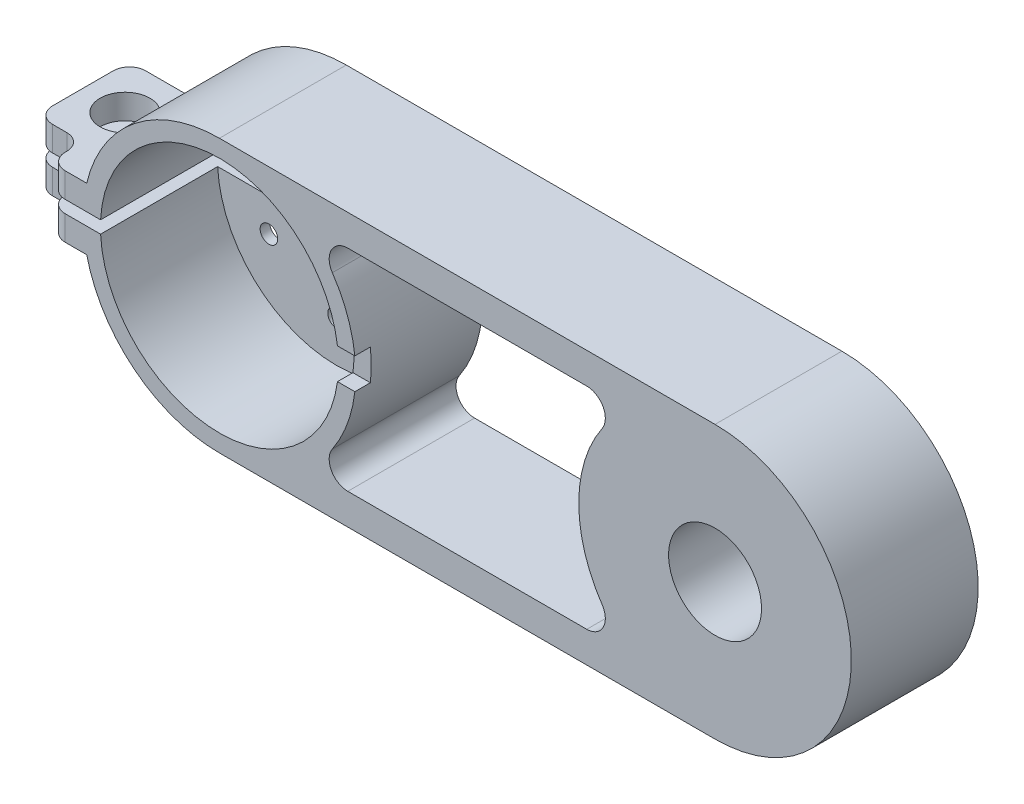
SolidWorks part; units mm, degrees
ref_plane "Front Plane" through (0, 0, 0) normal (0, 0, 1) x (1, 0, 0)
ref_plane "Top Plane" through (0, 0, 0) normal (0, 1, 0) x (1, 0, 0)
ref_plane "Right Plane" through (0, 0, 0) normal (1, 0, 0) x (0, 0, -1)
sketch "Sketch1" plane through (0, 0, 0) normal (0, 0, 1) x (1, 0, 0)
  line L0 (25.4, 0) -> (-25.4, 0) construction
  line L5 (25.4, -13.97) -> (-25.4, -13.97)
  line L6 (25.4, 13.97) -> (-25.4, 13.97)
  circle A0 centre (-25.4, 0) radius 8 construction
  arc A1 (25.4, -13.97) -> (25.4, 13.97) centre (25.4, 0) ccw
  arc A2 (-25.4, 13.97) -> (-25.4, -13.97) centre (-25.4, 0) ccw
  circle A3 centre (-25.4, 0) radius 12.7 construction
  circle A4 centre (25.4, 0) radius 38.1 construction
  circle A5 centre (-25.4, 0) radius 12.2
  point P2 (0, 0)
  dimension "D1" = 24.4
  dimension "mount spacing" = 16
  dimension "motor gear" = 25.4
  dimension "input gear" = 76.2
  dimension "D2" = 27.94
extrude "Boss-Extrude1" add sketch "Sketch1" along normal blind 13 contours A5 | L6 A2 L5 A1 A5 region at (7.5897, 0, 0) region at (-25.4, 0, 0)
hole_wizard "M1.6 Clearance Hole2" positions "Sketch4" profile "Sketch3" hole size "M1.6" standard "_Gentex Metric" end condition through all
sketch "Sketch4" plane through (0, 0, 13) normal (0, 0, 1) x (1, 0, 0)
  circle A0 centre (-25.4, 0) radius 8 construction
  point P5 (-25.4, 8)
  point P15 (-18.4718, 4)
  point P16 (-18.4718, -4)
  point P17 (-25.4, -8)
  point P18 (-32.3282, -4)
  point P19 (-32.3282, 4)
  dimension "D1" = 16
  dimension "D2" = 6
sketch "Sketch3" plane through (-32.3282, 4, 13) normal (1, 0, 0) x (0, -1, 0)
  line L0 (0, 0) -> (0, 13)
  line L1 (0, 13) -> (0.9, 13)
  line L2 (0.9, 13) -> (0.9, 0)
  line L5 (0.9, 0) -> (0, 0)
  line L11 (0, -6.35) -> (0, 107.95) construction
  dimension "Thru Hole Dia." = 1.8
  dimension "Thru Hole Depth" = 13
hole_wizard "3/8 (0.375) Diameter Hole1" positions "Sketch5" profile "Sketch6" hole size "3/8" standard "_Gentex Inch" end condition through all
sketch "Sketch5" plane through (0, 0, 13) normal (0, 0, 1) x (1, 0, 0)
  point P0 (25.4, 0)
sketch "Sketch6" plane through (25.4, 0, 13) normal (1, 0, 0) x (0, -1, 0)
  line L0 (0, 0) -> (0, 13)
  line L1 (0, 13) -> (4.7625, 13)
  line L2 (4.7625, 13) -> (4.7625, 0)
  line L5 (4.7625, 0) -> (0, 0)
  line L11 (0, -6.35) -> (0, 107.95) construction
  dimension "Thru Hole Dia." = 9.525
  dimension "Thru Hole Depth" = 13
extrude "Cut-Extrude1" cut sketch "Sketch1<4>" along normal through all from offset 1 contours A5 region at (-25.4, 0, 0)
sketch "Sketch1<4>" plane through (0, 0, 0) normal (0, 0, 1) x (1, 0, 0) same geometry as "Sketch1"
sketch "Sketch7" plane through (0, 0, 0) normal (0, 1, 0) x (1, 0, 0)
  line L0 (-38.1, 0) -> (-47.625, 0)
  line L1 (-25.4, 0) -> (-39.37, 0) construction
  line L2 (-47.625, 0) -> (-47.625, -9.525)
  line L3 (-47.625, -9.525) -> (-42.8625, -9.525)
  line L4 (-42.8625, -9.525) -> (-42.8625, -13)
  line L5 (-42.8625, -13) -> (-38.1, -13)
  line L7 (-38.1, 0) -> (0, 0) construction
  line L8 (-38.1, -13) -> (-38.1, 0)
  line L9 (-39.37, -13) -> (-25.4, -13) construction
  dimension "D1" = 9.525
  dimension "D2" = 38.1
extrude "Boss-Extrude2" add sketch "Sketch7" along normal mid plane 6.35
hole_wizard "#10 Clearance Hole1" positions "Sketch12" profile "Sketch11" hole size "#10" standard "_Gentex Inch" end condition through all
sketch "Sketch12" plane through (0, -3.175, 0) normal (0, -1, 0) x (-1, 0, 0)
  line L0 (47.625, -9.525) -> (43.3147, -4.7625) construction
  line L1 (43.3147, -4.7625) -> (39.0044, 0) construction
  point P0 (43.3147, -4.7625)
sketch "Sketch11" plane through (-43.3147, -3.175, 4.7625) normal (1, 0, 0) x (0, 0, -1)
  line L0 (0, 0) -> (0, 17.145)
  line L1 (0, 17.145) -> (2.5527, 17.145)
  line L2 (2.5527, 17.145) -> (2.5527, 0)
  line L5 (2.5527, 0) -> (0, 0)
  line L11 (0, -6.35) -> (0, 107.95) construction
  dimension "Thru Hole Dia." = 5.1054
  dimension "Thru Hole Depth" = 17.145
fillet "Fillet1" radius 1.651 4 edges at (-47.625, 0, 0) (-42.8625, 0, 13) (-42.8625, 0, 9.525) (-47.625, 0, 9.525)
sketch "Sketch9" plane through (0, 0, 13) normal (0, 0, 1) x (1, 0, 0)
  line L0 (-47.625, -3.175) -> (-47.625, 3.175) construction
  line L1 (-47.625, 0.635) -> (-29.0958, 0.635)
  line L2 (-47.625, 0.635) -> (-47.625, -0.635)
  line L3 (-47.625, -0.635) -> (-29.0958, -0.635)
  line L5 (-47.625, 0.635) -> (-29.0958, -0.635) construction
  line L6 (-47.625, -0.635) -> (-29.0958, 0.635) construction
  arc A0 (-29.0958, -0.635) -> (-29.0958, 0.635) centre (-25.4, 0) ccw
  circle A1 centre (-25.4, 0) radius 12.2 construction
  arc A2 (-29.0958, 0.635) -> (-29.0958, -0.635) centre (-25.4, 0) ccw
  point P6 (-38.3604, 0)
  line M4 (-41.2115, 3.175) -> (-41.2115, -3.175)
  circle M11 centre (-25.4, 0) radius 12.2
  dimension "D1" = 7.5
  dimension "D2" = 1.27
extrude "Cut-Extrude2" cut sketch "Sketch9" against normal through all contours A0 | A0 L1 L3 M11 | L2 L3 L1 M4 | L3 L1 M4 M11 region at (-44.4183, 0, 13) region at (-39.403, 0, 13) region at (-33.3632, 0, 13) region at (-25.4, 0, 13)
sketch "Sketch13" plane through (0, 0, 13) normal (0, 0, 1) x (1, 0, 0)
  line L5 (-16.5327, 10.795) -> (16.5327, 10.795)
  line L6 (-16.5327, -10.795) -> (16.5327, -10.795)
  line L7 (25.4, -13.97) -> (-25.4, -13.97) construction
  arc A0 (-16.5327, -10.795) -> (-16.5327, 10.795) centre (-25.4, 0) ccw
  arc A1 (16.5327, 10.795) -> (16.5327, -10.795) centre (25.4, 0) ccw
  arc A2 (-16.5327, 10.795) -> (-16.5327, -10.795) centre (-25.4, 0) ccw construction
  arc A3 (16.5327, -10.795) -> (16.5327, 10.795) centre (25.4, 0) ccw construction
  dimension "D1" = 3.175
extrude "Cut-Extrude3" cut sketch "Sketch13" against normal through all
fillet "Fillet2" radius 1.905 4 edges at (16.5327, -10.795, 6.5) (16.5327, 10.795, 6.5) (-16.5327, 10.795, 6.5) (-16.5327, -10.795, 6.5)
sketch "Sketch14" plane through (0, 0, 13) normal (0, 0, 1) x (1, 0, 0)
  line L0 (-25.4, 0) -> (0, 0) construction
  line L1 (-25.4, 1.5875) -> (0, 1.5875)
  line L2 (-25.4, -1.5875) -> (0, -1.5875)
  arc A0 (-25.4, 1.5875) -> (-25.4, -1.5875) centre (-25.4, 0) ccw
  arc A1 (0, -1.5875) -> (0, 1.5875) centre (0, 0) ccw
  point P4 (-12.7, 0)
  dimension "D1" = 3.175
extrude "Cut-Extrude4" cut sketch "Sketch14" against normal blind 1.5875
